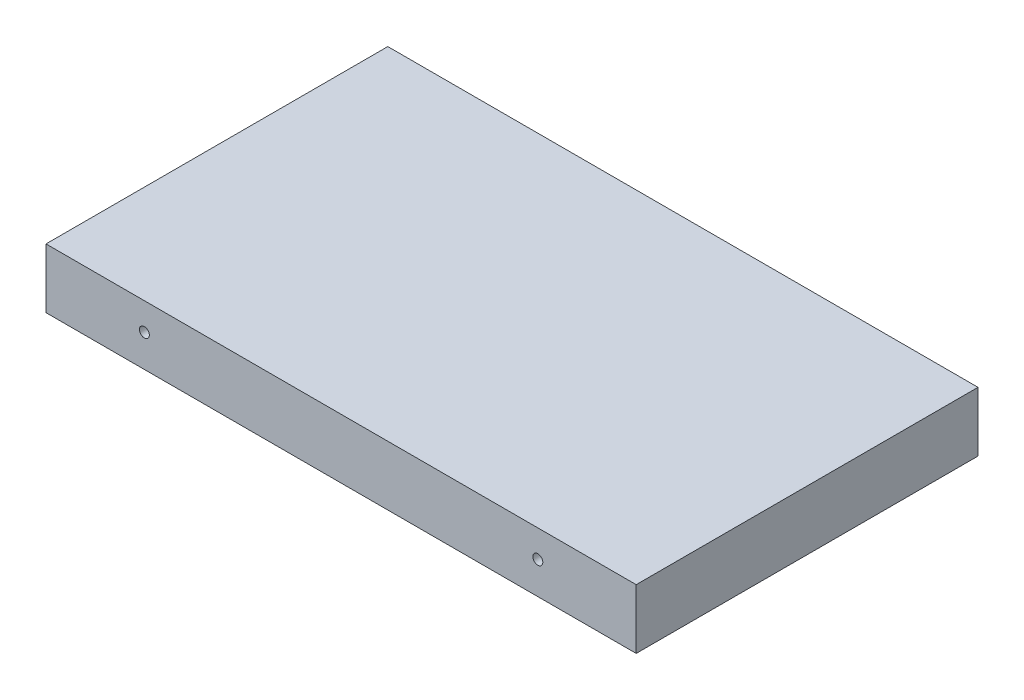
SolidWorks part; units mm, degrees
material "Beech"
ref_plane "Front Plane" through (0, 0, 0) normal (0, 0, 1) x (1, 0, 0)
ref_plane "Top Plane" through (0, 0, 0) normal (0, 1, 0) x (1, 0, 0)
ref_plane "Right Plane" through (0, 0, 0) normal (1, 0, 0) x (0, 0, -1)
sketch "Sketch1" plane through (0, 0, 0) normal (0, 0, 1) x (1, 0, 0)
  line L0 (-322.2545, -292.3211) -> (-133.5295, -292.3211) construction
  line L1 (-322.2545, -431.1858) -> (-322.2545, 0) construction
  line L2 (-133.5295, -157.3) -> (-133.5295, -431.1858) construction
  line L3 (8.6955, -157.3) -> (-256.7045, -157.3) construction
  line L4 (93.2955, -427.3421) -> (-341.3045, -427.3421) construction
  line L5 (-322.2545, -301.8461) -> (-133.5295, -301.8461)
  line L6 (-322.2545, -282.7961) -> (-133.5295, -282.7961)
  line L7 (-322.2545, -301.8461) -> (-322.2545, -282.7961)
  line L8 (-133.5295, -301.8461) -> (-133.5295, -282.7961)
  dimension "D1" = 9.525
  dimension "D2" = 9.525
extrude "Boss-Extrude1" add sketch "Sketch1" along normal up to surface (109.3 mm away)
hole_wizard "Hole1" positions "Sketch2" profile "Sketch3" legacy
sketch "Sketch2" plane through (-124.0045, 10.4243, -12.7) normal (0, 0, -1) x (1, 0, 0)
  line L1 (0, 465.9538) -> (0, 167.7243) construction
  point P1 (113.65, 128.8076)
  point P3 (113.65, 23.941)
  point P5 (-94.6, 161.3743)
  point P7 (94.6, 161.3743)
  point P9 (0, 161.3743)
  point P11 (0, 193.1243)
  point P13 (0, 440.5538)
  point P15 (0, 301.9704)
  point P17 (40.9792, 301.9704)
  point P19 (166.7958, 301.9704)
  point P21 (207.775, 440.5538)
  point P23 (207.775, 333.0214)
  point P25 (207.775, 225.489)
  point P27 (207.775, 137.4243)
  point P29 (207.775, 10.4243)
  point P33 (-207.775, 10.4243)
  point P34 (-207.775, 137.4243)
  point P35 (-207.775, 225.489)
  point P36 (-207.775, 333.0214)
  point P37 (-207.775, 440.5538)
  point P38 (-166.7958, 301.9704)
  point P39 (-40.9792, 301.9704)
  point P40 (-113.65, 23.941)
  point P41 (-113.65, 128.8076)
sketch "Sketch3" plane through (-10.3545, -118.3833, -12.7) normal (1, 0, 0) x (0, 1, 0)
  line L0 (0, 0) -> (0, 32.7039)
  line L1 (0, 32.7039) -> (1.5875, 31.75)
  line L2 (1.5875, 31.75) -> (1.5875, 4.0177)
  line L3 (1.5875, 4.0177) -> (5.08, 0)
  line L4 (5.08, 0) -> (0, 0)
  line L5 (0, -14.3089) -> (0, 102.4216) construction
  line L6 (0, 32.7039) -> (-1.5875, 31.75) construction
  line L7 (-1.5875, 4.0177) -> (-5.08, 0) construction
  dimension "Diameter" = 3.175
  dimension "Depth" = 31.75
  dimension "C-Sink Diameter" = 10.16
  dimension "C-Sink Angle" = 82
  dimension "Drill Angle" = 118
hole_wizard "Hole2" positions "Sketch4" profile "Sketch5" legacy
sketch "Sketch4" plane through (-124.0045, 10.4243, 122) normal (0, 0, 1) x (-1, 0, 0)
  line L1 (0, 465.9538) -> (0, 167.7243) construction
  point P1 (113.65, 128.8076)
  point P3 (113.65, 23.941)
  point P5 (-94.6, 161.3743)
  point P7 (94.6, 161.3743)
  point P9 (0, 161.3743)
  point P11 (0, 193.1243)
  point P13 (0, 440.5538)
  point P15 (0, 301.9704)
  point P17 (40.9792, 301.9704)
  point P19 (166.7958, 301.9704)
  point P21 (207.775, 440.5538)
  point P23 (207.775, 333.0214)
  point P25 (207.775, 225.489)
  point P27 (207.775, 137.4243)
  point P29 (207.775, 10.4243)
  point P33 (-207.775, 10.4243)
  point P34 (-207.775, 137.4243)
  point P35 (-207.775, 225.489)
  point P36 (-207.775, 333.0214)
  point P37 (-207.775, 440.5538)
  point P38 (-166.7958, 301.9704)
  point P39 (-40.9792, 301.9704)
  point P40 (-113.65, 23.941)
  point P41 (-113.65, 128.8076)
sketch "Sketch5" plane through (-237.6545, -118.3833, 122) normal (1, 0, 0) x (0, -1, 0)
  line L0 (0, 0) -> (0, 32.7039)
  line L1 (0, 32.7039) -> (1.5875, 31.75)
  line L2 (1.5875, 31.75) -> (1.5875, 4.0177)
  line L3 (1.5875, 4.0177) -> (5.08, 0)
  line L4 (5.08, 0) -> (0, 0)
  line L5 (0, -14.3089) -> (0, 102.4216) construction
  line L6 (0, 32.7039) -> (-1.5875, 31.75) construction
  line L7 (-1.5875, 4.0177) -> (-5.08, 0) construction
  dimension "Diameter" = 3.175
  dimension "Depth" = 31.75
  dimension "C-Sink Diameter" = 10.16
  dimension "C-Sink Angle" = 82
  dimension "Drill Angle" = 118
hole_wizard "Hole3" positions "Sketch6" profile "Sketch7" legacy
sketch "Sketch6" plane through (-124.0045, 10.4243, 122) normal (0, 0, 1) x (-1, 0, 0)
  line L12 (0, 0) -> (0, 155.0243) construction
  point P0 (-207.775, 333.0214)
  point P3 (-207.775, 225.489)
  point P6 (-207.775, 137.4243)
  point P9 (-172.1667, 4.0743)
  point P12 (-146.0833, 4.0743)
  point P15 (-94.6, 161.3743)
  point P18 (0, 161.3743)
  point P21 (94.6, 161.3743)
  point P24 (146.0833, 4.0743)
  point P27 (172.1667, 4.0743)
  point P30 (207.775, 137.4243)
  point P33 (207.775, 225.489)
  point P36 (207.775, 333.0214)
  point P39 (166.7958, 301.9704)
  point P42 (40.9792, 301.9704)
  point P45 (-40.9792, 301.9704)
  point P48 (-166.7958, 301.9704)
  point P51 (0, 193.1243)
  point P54 (0, 301.9704)
  point P57 (0, 412.3664)
  point P80 (-126.35, 106.8243)
  point P82 (-126.35, 58.6243)
  point P96 (126.35, 58.6243)
  point P97 (126.35, 106.8243)
sketch "Sketch7" plane through (83.7705, -322.5971, 122) normal (1, 0, 0) x (0, -1, 0)
  line L0 (0, 0) -> (0, 32.7039)
  line L1 (0, 32.7039) -> (1.5875, 31.75)
  line L2 (1.5875, 31.75) -> (1.5875, 4.0177)
  line L3 (1.5875, 4.0177) -> (5.08, 0)
  line L4 (5.08, 0) -> (0, 0)
  line L5 (0, -14.3089) -> (0, 102.4216) construction
  line L6 (0, 32.7039) -> (-1.5875, 31.75) construction
  line L7 (-1.5875, 4.0177) -> (-5.08, 0) construction
  dimension "Diameter" = 3.175
  dimension "Depth" = 31.75
  dimension "C-Sink Diameter" = 10.16
  dimension "C-Sink Angle" = 82
  dimension "Drill Angle" = 118
